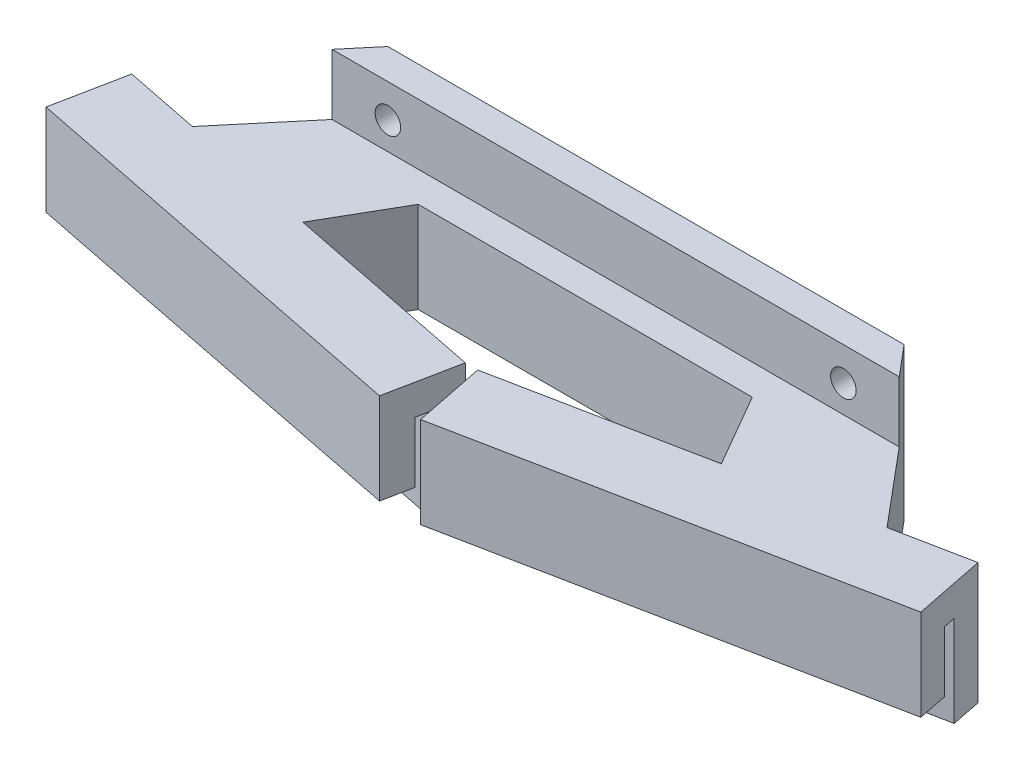
SolidWorks part; units mm, degrees
material "ABS"
ref_plane "Front Plane" through (0, 0, 0) normal (0, 0, 1) x (1, 0, 0)
ref_plane "Top Plane" through (0, 0, 0) normal (0, 1, 0) x (1, 0, 0)
ref_plane "Right Plane" through (0, 0, 0) normal (1, 0, 0) x (0, 0, -1)
ref_axis "X" through (-88.99, 0, 0) along (1, 0, 0)
ref_axis "Y" through (0, 55, 0) along (0, -1, 0)
ref_axis "Z" through (0, 0, -88.99) along (0, 0, 1)
sketch "Sketch1" plane through (0, 0, 0) normal (0, 1, 0) x (1, 0, 0)
  line L0 (27.1702, -94.8196) -> (25.1643, -95.2208) construction
  line L1 (27.1702, -94.8196) -> (27.5625, -96.7807)
  line L2 (25.1643, -95.2208) -> (23.1583, -94.8196) construction
  line L3 (22.9622, -95.8001) -> (27.3663, -95.8001) construction
  line L4 (22.7661, -96.7807) -> (23.1583, -94.8196)
  line L6 (23.1583, -94.8196) -> (-45.4823, -81.0914)
  line L7 (-45.4823, -81.0914) -> (-45.8746, -83.0526)
  line L8 (-45.8746, -83.0526) -> (22.7661, -96.7807)
  line L9 (27.1702, -94.8196) -> (95.8109, -81.0914)
  line L10 (95.8109, -81.0914) -> (96.2031, -83.0526)
  line L11 (96.2031, -83.0526) -> (27.5625, -96.7807)
  dimension "D1" = 4.4042
  dimension "D3" = 2
  dimension "D4" = 2
  dimension "D7" = 70
  dimension "D8" = 70
extrude "Boss-Extrude1" add sketch "Sketch1" along normal blind 5
sketch "Sketch2" plane through (0, 5, 0) normal (0, 1, 0) x (1, 0, 0)
  line L0 (0, 0) -> (0, 33.2136) construction
  line L1 (22.9622, -95.8001) -> (-45.6785, -82.072) construction
  line L2 (22.7661, -96.7807) -> (23.1583, -94.8196) construction
  line L3 (-45.4823, -81.0914) -> (-45.8746, -83.0526) construction
  line L4 (-45.4823, -81.0914) -> (-44.5018, -76.1885)
  line L5 (-44.5018, -76.1885) -> (24.1389, -89.9167)
  line L6 (24.1389, -89.9167) -> (23.1583, -94.8196)
  line L7 (23.1583, -94.8196) -> (-45.4823, -81.0914) construction
  line L8 (23.1583, -94.8196) -> (-45.4823, -81.0914)
  line L9 (21.7855, -101.6836) -> (22.7661, -96.7807)
  line L10 (-46.8552, -87.9555) -> (21.7855, -101.6836)
  line L11 (-45.8746, -83.0526) -> (-46.8552, -87.9555)
  line L12 (22.7661, -96.7807) -> (-45.8746, -83.0526)
  line L21 (27.1702, -94.8196) -> (26.1896, -89.9167)
  line L22 (26.1896, -89.9167) -> (94.8303, -76.1885)
  line L23 (94.8303, -76.1885) -> (95.8109, -81.0914)
  line L24 (96.2031, -83.0526) -> (95.8109, -81.0914) construction
  line L25 (95.8109, -81.0914) -> (27.1702, -94.8196) construction
  line L26 (95.8109, -81.0914) -> (27.1702, -94.8196)
  line L27 (27.3663, -95.8001) -> (96.007, -82.072) construction
  line L28 (27.1702, -94.8196) -> (27.5625, -96.7807) construction
  line L29 (97.1837, -87.9555) -> (96.2031, -83.0526)
  line L30 (28.543, -101.6836) -> (97.1837, -87.9555)
  line L31 (27.5625, -96.7807) -> (28.543, -101.6836)
  line L32 (96.2031, -83.0526) -> (27.5625, -96.7807)
  dimension "D1" = 5
  dimension "D2" = 5
extrude "Boss-Extrude2" add sketch "Sketch2" against normal blind 20
ref_plane "Plane1" through (0, -10, 0) normal (0, 1, 0) x (1, 0, 0)
sketch "Sketch3" plane through (0, -10, 0) normal (0, 1, 0) x (1, 0, 0)
  line L0 (25.1643, -107.258) -> (25.1643, -89.9167) construction
  line L1 (-17.3357, -61.1885) -> (67.6643, -61.1885)
  line L3 (-2.3357, -71.1885) -> (52.6643, -71.1885)
  line L5 (24.1389, -89.9167) -> (26.1896, -89.9167) construction
  line L6 (-17.3357, -61.1885) -> (-32.0174, -78.6854)
  line L7 (24.1389, -89.9167) -> (-44.5018, -76.1885) construction
  line L8 (-2.3357, -71.1885) -> (-9.2886, -83.2312)
  line L9 (67.6643, -61.1885) -> (82.3459, -78.6854)
  line L10 (94.8303, -76.1885) -> (26.1896, -89.9167) construction
  line L11 (52.6643, -71.1885) -> (59.6171, -83.2312)
  line L12 (-32.0174, -78.6854) -> (-9.2886, -83.2312)
  line L13 (59.6171, -83.2312) -> (82.3459, -78.6854)
  point P5 (25.1643, -71.1885)
  point P10 (25.1643, -89.9167)
  dimension "D1" = 10
  dimension "D2" = 15
  dimension "D3" = 15
  dimension "D4" = 85
  dimension "D5" = 120
  dimension "D6" = 120
  dimension "D7" = 130
  dimension "D8" = 130
  dimension "D9" = 15
extrude "Boss-Extrude3" add sketch "Sketch3" along normal blind 5
sketch "Sketch4" plane through (0, -5, 0) normal (0, 1, 0) x (1, 0, 0)
  line L0 (-17.3357, -61.1885) -> (-17.3357, -56.1885)
  line L1 (-17.3357, -56.1885) -> (67.6643, -56.1885)
  line L2 (67.6643, -56.1885) -> (67.6643, -61.1885)
  line L3 (67.6643, -61.1885) -> (-17.3357, -61.1885)
  dimension "D1" = 5
extrude "Boss-Extrude4" add sketch "Sketch4" against normal up to surface (5 mm away) up to face at (25.1643, -10, 73.5734)
sketch "Sketch5" plane through (0, -5, 0) normal (0, 1, 0) x (1, 0, 0)
  line L0 (25.1643, -71.1885) -> (25.1643, -56.1885) construction
  line L7 (-21.5312, -66.1885) -> (71.8598, -66.1885)
  line L9 (-2.3357, -71.1885) -> (52.6643, -71.1885) construction
  line L10 (67.6643, -56.1885) -> (-17.3357, -56.1885) construction
  line L13 (82.3459, -78.6854) -> (67.6643, -61.1885) construction
  line L14 (-17.3357, -61.1885) -> (67.6643, -61.1885)
  line L16 (-17.3357, -56.1885) -> (-17.3357, -61.1885) construction
  line L17 (67.6643, -61.1885) -> (67.6643, -56.1885) construction
  line L18 (67.6643, -61.1885) -> (71.8598, -66.1885)
  line L19 (-21.5312, -66.1885) -> (-17.3357, -61.1885)
  point P10 (25.1643, -66.1885)
  dimension "D1" = 5
  dimension "D3" = 5
extrude "Boss-Extrude5" add sketch "Sketch5" along normal blind 20
sketch "Sketch7" plane through (0, 0, 66.1885) normal (0, 0, 1) x (1, 0, 0)
  line L0 (-12.3357, 9.5) -> (62.6643, 9.5) construction
  line L1 (25.1643, 15) -> (25.1643, -5) construction
  line L2 (-21.5312, 15) -> (71.8598, 15) construction
  line L3 (-2.3357, -5) -> (52.6643, -5) construction
  line L4 (-21.5312, -5) -> (71.8598, -5) construction
  circle A0 centre (-12.3357, 9.5) radius 2.1
  circle A1 centre (62.6643, 9.5) radius 2.1
  point P10 (25.1643, 9.5)
  dimension "D1" = 4.2
  dimension "D2" = 75
  dimension "D3" = 14.5
extrude "Cut-Extrude1" cut sketch "Sketch7" against normal up to surface (5 mm away) up to face at (25.1643, 5, 61.1885)
sketch "Sketch8" plane through (0, -5, 0) normal (0, 1, 0) x (1, 0, 0)
  line L0 (59.6171, -83.2312) -> (82.3459, -78.6854) construction
  line L1 (52.6643, -71.1885) -> (59.6171, -83.2312) construction
  line L2 (82.3459, -78.6854) -> (71.8598, -66.1885) construction
  line L3 (-2.3357, -71.1885) -> (52.6643, -71.1885) construction
  line L4 (-9.2886, -83.2312) -> (-2.3357, -71.1885) construction
  line L5 (-21.5312, -66.1885) -> (71.8598, -66.1885) construction
  line L6 (-32.0174, -78.6854) -> (-9.2886, -83.2312) construction
  line L7 (-21.5312, -66.1885) -> (-32.0174, -78.6854) construction
  line L8 (59.6171, -83.2312) -> (82.3459, -78.6854)
  line L9 (52.6643, -71.1885) -> (59.6171, -83.2312)
  line L10 (82.3459, -78.6854) -> (71.8598, -66.1885)
  line L11 (-2.3357, -71.1885) -> (52.6643, -71.1885)
  line L12 (-9.2886, -83.2312) -> (-2.3357, -71.1885)
  line L13 (-21.5312, -66.1885) -> (71.8598, -66.1885)
  line L14 (-32.0174, -78.6854) -> (-9.2886, -83.2312)
  line L15 (-21.5312, -66.1885) -> (-32.0174, -78.6854)
extrude "Boss-Extrude6" add sketch "Sketch8" along normal up to surface (10 mm away) up to face at (-11.3581, 5, 88.9361)
sketch "Sketch11" plane through (0, -5, 0) normal (0, 1, 0) x (1, 0, 0)
  line L1 (-17.3357, -56.1885) -> (67.6643, -56.1885)
  line L2 (-17.3357, -56.1885) -> (-17.3357, -61.1885)
  line L3 (-17.3357, -61.1885) -> (67.6643, -61.1885)
  line L4 (67.6643, -56.1885) -> (67.6643, -61.1885)
extrude "Cut-Extrude2" cut sketch "Sketch11" against normal up to surface (5 mm away) up to face at (25.1643, -10, 70.0964)
sketch "Sketch12" plane through (0, -15, 0) normal (0, -1, 0) x (1, 0, 0)
  line L0 (97.1837, 87.9555) -> (28.543, 101.6836) construction
  line L1 (28.543, 101.6836) -> (27.5625, 96.7807) construction
  line L2 (27.5625, 96.7807) -> (96.2031, 83.0526) construction
  line L3 (96.2031, 83.0526) -> (97.1837, 87.9555) construction
  line L4 (21.7855, 101.6836) -> (-46.8552, 87.9555) construction
  line L5 (-46.8552, 87.9555) -> (-45.8746, 83.0526) construction
  line L6 (-45.8746, 83.0526) -> (22.7661, 96.7807) construction
  line L7 (22.7661, 96.7807) -> (21.7855, 101.6836) construction
  line L8 (97.1837, 87.9555) -> (28.543, 101.6836)
  line L9 (28.543, 101.6836) -> (27.5625, 96.7807)
  line L10 (27.5625, 96.7807) -> (96.2031, 83.0526)
  line L11 (96.2031, 83.0526) -> (97.1837, 87.9555)
  line L12 (21.7855, 101.6836) -> (-46.8552, 87.9555)
  line L13 (-46.8552, 87.9555) -> (-45.8746, 83.0526)
  line L14 (-45.8746, 83.0526) -> (22.7661, 96.7807)
  line L15 (22.7661, 96.7807) -> (21.7855, 101.6836)
extrude "Cut-Extrude3" cut sketch "Sketch12" against normal blind 5
